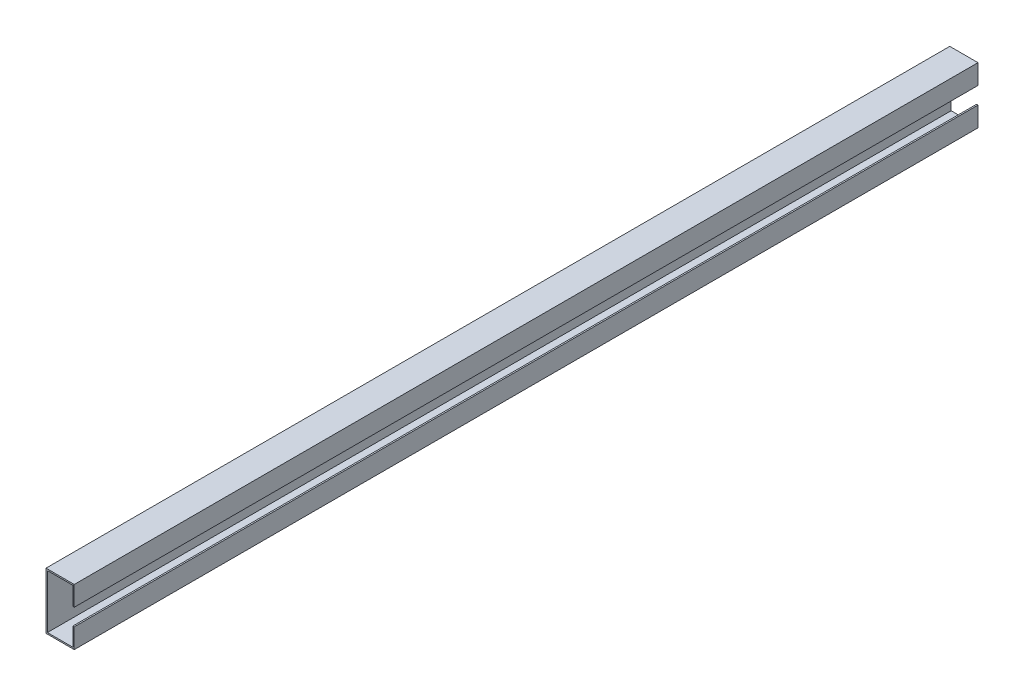
SolidWorks part; units mm, degrees
ref_plane "Alzado" through (0, 0, 0) normal (0, 0, 1) x (1, 0, 0)
ref_plane "Planta" through (0, 0, 0) normal (0, 1, 0) x (1, 0, 0)
ref_plane "Vista lateral" through (0, 0, 0) normal (1, 0, 0) x (0, 0, -1)
sketch "Croquis1" plane through (0, 0, 0) normal (0, 0, 1) x (1, 0, 0)
  line L0 (-22.5, -47.5) -> (-22.5, 47.5)
  line L1 (-25, -50) -> (25, -50)
  line L2 (-25, -50) -> (-25, 50)
  line L3 (-25, 50) -> (25, 50)
  line L4 (25, -50) -> (25, 50)
  line L5 (-25, -50) -> (25, 50) construction
  line L6 (-25, 50) -> (25, -50) construction
  line L7 (-22.5, 47.5) -> (22.5, 47.5)
  line L8 (22.5, -47.5) -> (22.5, 47.5)
  line L9 (-22.5, -47.5) -> (22.5, -47.5)
  point P0 (0, 0)
  dimension "D1" = 100
  dimension "D2" = 50
  dimension "D3" = 2.5
extrude "Saliente-Extruir1" add sketch "Croquis1" along normal mid plane 1600
sketch "Croquis2" plane through (25, 0, 0) normal (1, 0, 0) x (0, 0, -1)
  line L1 (800, 15) -> (-800, 15)
  line L2 (800, 15) -> (800, -15)
  line L3 (800, -15) -> (-800, -15)
  line L4 (-800, 15) -> (-800, -15)
  line L5 (800, 15) -> (-800, -15) construction
  line L6 (800, -15) -> (-800, 15) construction
  point P0 (0, 0)
  dimension "D1" = 1600
  dimension "D2" = 30
extrude "Cortar-Extruir1" cut sketch "Croquis2" against normal blind 5
sketch "Croquis8" plane through (-25, 0, 0) normal (-1, 0, 0) x (0, 0, 1)
  line L0 (850.2048, 0) -> (-1024.1629, 0) construction
  line L1 (0, 0) -> (100, 0) construction
  line L2 (0, 0) -> (-100, 0) construction
  circle A0 centre (0, 0) radius 7.1437
  circle A1 centre (100, 0) radius 7.1438
  circle A2 centre (200, 0) radius 7.1437
  circle A3 centre (300, 0) radius 7.1438
  circle A4 centre (400, 0) radius 7.1438
  circle A5 centre (500, 0) radius 7.1437
  circle A6 centre (600, 0) radius 7.1437
  circle A7 centre (700, 0) radius 7.1437
  circle A8 centre (-100, 0) radius 7.1438
  circle A9 centre (-200, 0) radius 7.1437
  circle A10 centre (-300, 0) radius 7.1438
  circle A11 centre (-400, 0) radius 7.1438
  circle A12 centre (-500, 0) radius 7.1438
  circle A13 centre (-600, 0) radius 7.1437
  circle A14 centre (-700, 0) radius 7.1437
  dimension "D1" = 14.2875
  dimension "D3" = 100
  dimension "D5" = 100
  dimension "D2" = 8
  dimension "D4" = 8
extrude "Cortar-Extruir3" cut sketch "Croquis8" against normal through all
